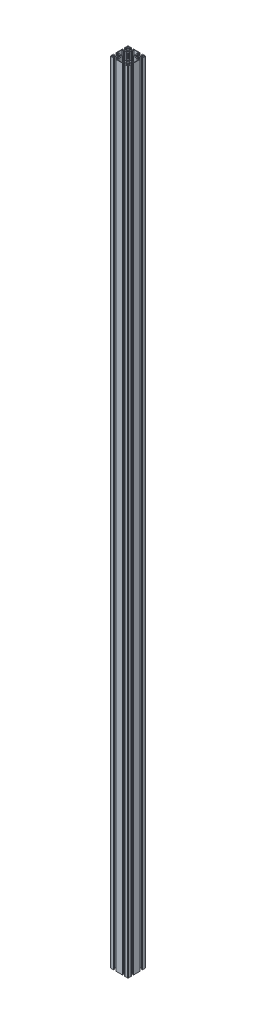
SolidWorks part; units mm, degrees
material "6061 Alloy"
ref_plane "Front Plane" through (0, 0, 0) normal (0, 0, 1) x (1, 0, 0)
ref_plane "Top Plane" through (0, 0, 0) normal (0, 1, 0) x (1, 0, 0)
ref_plane "Right Plane" through (0, 0, 0) normal (1, 0, 0) x (0, 0, -1)
sketch "Sketch1" plane through (0, 0, 0) normal (0, 1, 0) x (1, 0, 0)
  line L0 (505.2058, 27.1189) -> (507.2058, 27.1189)
  line L1 (507.2058, 25.1189) -> (496.7058, 25.1189)
  line L2 (495.7058, 26.1189) -> (495.7058, 36.6189)
  line L3 (497.7058, 36.6189) -> (497.7058, 34.6189)
  line L4 (498.7058, 33.6189) -> (503.8258, 33.6189)
  line L5 (504.2058, 33.2389) -> (504.2058, 28.1189)
  line L6 (522.0488, 41.8952) -> (520.4218, 42.9309)
  line L7 (518.8935, 41.4027) -> (519.9294, 39.776)
  line L8 (517.7043, 38.8542) -> (517.2863, 40.7371)
  line L9 (515.125, 40.7371) -> (514.7072, 38.8544)
  line L10 (512.482, 39.776) -> (513.5178, 41.4029)
  line L11 (511.9896, 42.9313) -> (510.3629, 41.8954)
  line L12 (509.4411, 44.1204) -> (511.324, 44.5385)
  line L13 (511.324, 46.6998) -> (509.4413, 47.1175)
  line L14 (510.3628, 49.3427) -> (511.9898, 48.3069)
  line L15 (513.5181, 49.8351) -> (512.4822, 51.4618)
  line L16 (514.7073, 52.3836) -> (515.1254, 50.5008)
  line L17 (517.2867, 50.5007) -> (517.7044, 52.3835)
  line L18 (519.9296, 51.4619) -> (518.8938, 49.8349)
  line L19 (520.422, 48.3066) -> (522.0487, 49.3425)
  line L20 (522.9705, 47.1174) -> (521.0877, 46.6994)
  line L21 (521.0876, 44.5381) -> (522.9703, 44.1203)
  line L22 (579.7058, 34.6189) -> (579.7058, 36.6189)
  line L23 (581.7058, 36.6189) -> (581.7058, 26.1189)
  line L24 (580.7058, 25.1189) -> (570.2058, 25.1189)
  line L25 (570.2058, 27.1189) -> (572.2058, 27.1189)
  line L26 (573.2058, 28.1189) -> (573.2058, 33.2389)
  line L27 (573.5858, 33.6189) -> (578.7058, 33.6189)
  line L28 (565.422, 48.3066) -> (567.0487, 49.3425)
  line L29 (567.9705, 47.1174) -> (566.0877, 46.6994)
  line L30 (566.0876, 44.5381) -> (567.9703, 44.1203)
  line L31 (567.0488, 41.8952) -> (565.4218, 42.9309)
  line L32 (563.8935, 41.4027) -> (564.9294, 39.776)
  line L33 (562.7043, 38.8542) -> (562.2863, 40.7371)
  line L34 (560.125, 40.7371) -> (559.7072, 38.8544)
  line L35 (557.482, 39.776) -> (558.5178, 41.4029)
  line L36 (556.9896, 42.9313) -> (555.3629, 41.8954)
  line L37 (554.4411, 44.1204) -> (556.324, 44.5385)
  line L38 (556.324, 46.6998) -> (554.4413, 47.1175)
  line L39 (555.3628, 49.3427) -> (556.9898, 48.3069)
  line L40 (558.5181, 49.8351) -> (557.4822, 51.4618)
  line L41 (559.7073, 52.3836) -> (560.1254, 50.5008)
  line L42 (562.2867, 50.5007) -> (562.7044, 52.3835)
  line L43 (564.9296, 51.4619) -> (563.8938, 49.8349)
  line L44 (573.2058, 102.9989) -> (573.2058, 108.1189)
  line L45 (572.2058, 109.1189) -> (570.2058, 109.1189)
  line L46 (570.2058, 111.1189) -> (580.7058, 111.1189)
  line L47 (581.7058, 110.1189) -> (581.7058, 99.6189)
  line L48 (579.7058, 99.6189) -> (579.7058, 101.6189)
  line L49 (578.7058, 102.6189) -> (573.5858, 102.6189)
  line L50 (565.422, 93.3066) -> (567.0487, 94.3425)
  line L51 (567.9705, 92.1174) -> (566.0877, 91.6994)
  line L52 (566.0876, 89.5381) -> (567.9703, 89.1203)
  line L53 (567.0488, 86.8952) -> (565.4218, 87.9309)
  line L54 (563.8935, 86.4027) -> (564.9294, 84.776)
  line L55 (562.7043, 83.8542) -> (562.2863, 85.7371)
  line L56 (560.125, 85.7371) -> (559.7072, 83.8544)
  line L57 (557.482, 84.776) -> (558.5178, 86.4029)
  line L58 (556.9896, 87.9313) -> (555.3629, 86.8954)
  line L59 (554.4411, 89.1204) -> (556.324, 89.5385)
  line L60 (556.324, 91.6998) -> (554.4413, 92.1175)
  line L61 (555.3628, 94.3427) -> (556.9898, 93.3069)
  line L62 (558.5181, 94.8351) -> (557.4822, 96.4618)
  line L63 (559.7073, 97.3836) -> (560.1254, 95.5008)
  line L64 (562.2867, 95.5007) -> (562.7044, 97.3835)
  line L65 (564.9296, 96.4619) -> (563.8938, 94.8349)
  line L66 (497.7058, 101.6189) -> (497.7058, 99.6189)
  line L67 (495.7058, 99.6189) -> (495.7058, 110.1189)
  line L68 (496.7058, 111.1189) -> (507.2058, 111.1189)
  line L69 (507.2058, 109.1189) -> (505.2058, 109.1189)
  line L70 (504.2058, 108.1189) -> (504.2058, 102.9989)
  line L71 (503.8258, 102.6189) -> (498.7058, 102.6189)
  line L72 (522.0488, 86.8952) -> (520.4218, 87.9309)
  line L73 (518.8935, 86.4027) -> (519.9294, 84.776)
  line L74 (517.7043, 83.8542) -> (517.2863, 85.7371)
  line L75 (515.125, 85.7371) -> (514.7072, 83.8544)
  line L76 (512.482, 84.776) -> (513.5178, 86.4029)
  line L77 (511.9896, 87.9313) -> (510.3629, 86.8954)
  line L78 (509.4411, 89.1204) -> (511.324, 89.5385)
  line L79 (511.324, 91.6998) -> (509.4413, 92.1175)
  line L80 (510.3628, 94.3427) -> (511.9898, 93.3069)
  line L81 (513.5181, 94.8351) -> (512.4822, 96.4618)
  line L82 (514.7073, 97.3836) -> (515.1254, 95.5008)
  line L83 (517.2867, 95.5007) -> (517.7044, 97.3835)
  line L84 (519.9296, 96.4619) -> (518.8938, 94.8349)
  line L85 (520.422, 93.3066) -> (522.0487, 94.3425)
  line L86 (522.9705, 92.1174) -> (521.0877, 91.6994)
  line L87 (521.0876, 89.5381) -> (522.9703, 89.1203)
  line L88 (577.7058, 57.9589) -> (572.0832, 57.9589)
  line L89 (570.669, 57.3731) -> (568.5261, 55.2302)
  line L90 (568.2574, 55.1189) -> (562.1058, 55.1189)
  line L91 (562.1058, 55.1189) -> (561.2058, 54.6038)
  line L92 (561.2058, 54.6038) -> (560.3058, 55.1189)
  line L93 (560.3058, 55.1189) -> (553.7058, 55.1189)
  line L94 (551.7058, 53.1189) -> (551.7058, 46.5189)
  line L95 (551.7058, 46.5189) -> (552.2254, 45.6189)
  line L96 (552.2254, 45.6189) -> (551.7058, 44.7189)
  line L97 (551.7058, 44.7189) -> (551.7058, 38.5674)
  line L98 (551.5945, 38.2987) -> (550.0845, 36.7886)
  line L99 (549.2058, 34.6673) -> (549.2058, 28.1189)
  line L100 (550.2058, 27.1189) -> (552.2058, 27.1189)
  line L101 (552.2058, 25.1189) -> (525.2058, 25.1189)
  line L102 (525.2058, 27.1189) -> (527.2058, 27.1189)
  line L103 (528.2058, 28.1189) -> (528.2058, 34.6673)
  line L104 (527.3271, 36.7886) -> (525.8171, 38.2987)
  line L105 (525.7058, 38.5674) -> (525.7058, 44.7189)
  line L106 (525.7058, 44.7189) -> (525.1862, 45.6189)
  line L107 (525.1862, 45.6189) -> (525.7058, 46.5189)
  line L108 (525.7058, 46.5189) -> (525.7058, 53.1189)
  line L109 (523.7058, 55.1189) -> (517.1058, 55.1189)
  line L110 (517.1058, 55.1189) -> (516.2058, 54.6038)
  line L111 (516.2058, 54.6038) -> (515.3058, 55.1189)
  line L112 (515.3058, 55.1189) -> (509.1542, 55.1189)
  line L113 (508.8855, 55.2302) -> (506.7426, 57.3731)
  line L114 (505.3284, 57.9589) -> (499.7058, 57.9589)
  line L115 (497.7058, 55.9589) -> (497.7058, 54.6189)
  line L116 (495.7058, 54.6189) -> (495.7058, 81.6189)
  line L117 (497.7058, 81.6189) -> (497.7058, 80.2789)
  line L118 (499.7058, 78.2789) -> (505.3284, 78.2789)
  line L119 (506.7426, 78.8647) -> (508.8855, 81.0076)
  line L120 (509.1542, 81.1189) -> (515.3058, 81.1189)
  line L121 (515.3058, 81.1189) -> (516.2058, 81.6341)
  line L122 (516.2058, 81.6341) -> (517.1058, 81.1189)
  line L123 (517.1058, 81.1189) -> (523.7058, 81.1189)
  line L124 (525.7058, 83.1189) -> (525.7058, 89.7189)
  line L125 (525.7058, 89.7189) -> (525.1862, 90.6189)
  line L126 (525.1862, 90.6189) -> (525.7058, 91.5189)
  line L127 (525.7058, 91.5189) -> (525.7058, 97.6705)
  line L128 (525.8171, 97.9392) -> (527.3271, 99.4492)
  line L129 (528.2058, 101.5705) -> (528.2058, 108.1189)
  line L130 (527.2058, 109.1189) -> (525.2058, 109.1189)
  line L131 (525.2058, 111.1189) -> (552.2058, 111.1189)
  line L132 (552.2058, 109.1189) -> (550.2058, 109.1189)
  line L133 (549.2058, 108.1189) -> (549.2058, 101.5705)
  line L134 (550.0845, 99.4492) -> (551.5945, 97.9392)
  line L135 (551.7058, 97.6705) -> (551.7058, 91.5189)
  line L136 (551.7058, 91.5189) -> (552.2254, 90.6189)
  line L137 (552.2254, 90.6189) -> (551.7058, 89.7189)
  line L138 (551.7058, 89.7189) -> (551.7058, 83.1189)
  line L139 (553.7058, 81.1189) -> (560.3058, 81.1189)
  line L140 (560.3058, 81.1189) -> (561.2058, 81.6341)
  line L141 (561.2058, 81.6341) -> (562.1058, 81.1189)
  line L142 (562.1058, 81.1189) -> (568.2574, 81.1189)
  line L143 (568.5261, 81.0076) -> (570.6639, 78.8698)
  line L144 (572.0781, 78.284) -> (577.7058, 78.284)
  line L145 (579.7058, 80.284) -> (579.7058, 81.6189)
  line L146 (581.7058, 81.6189) -> (581.7058, 54.6189)
  line L147 (579.7058, 54.6189) -> (579.7058, 55.9589)
  line L148 (583.7058, 52.2039) -> (583.7058, 84.0339)
  line L149 (582.1858, 85.5539) -> (579.2258, 85.5539)
  line L150 (577.7058, 84.0339) -> (577.7058, 81.5689)
  line L151 (576.7058, 80.5689) -> (573.7042, 80.5689)
  line L152 (573.4355, 80.6802) -> (570.8171, 83.2987)
  line L153 (570.7058, 83.5674) -> (570.7058, 89.7189)
  line L154 (570.7058, 89.7189) -> (570.1862, 90.6189)
  line L155 (570.1862, 90.6189) -> (570.7058, 91.5189)
  line L156 (570.7058, 91.5189) -> (570.7058, 97.6705)
  line L157 (570.8171, 97.9392) -> (573.4355, 100.5576)
  line L158 (573.7042, 100.6689) -> (576.7058, 100.6689)
  line L159 (577.7058, 99.6689) -> (577.7058, 97.2039)
  line L160 (579.2258, 95.6839) -> (582.1858, 95.6839)
  line L161 (583.7058, 97.2039) -> (583.7058, 110.1189)
  line L162 (580.7058, 113.1189) -> (567.7908, 113.1189)
  line L163 (566.2708, 111.5989) -> (566.2708, 108.6389)
  line L164 (567.7908, 107.1189) -> (570.2558, 107.1189)
  line L165 (571.2558, 106.1189) -> (571.2558, 103.1174)
  line L166 (571.1445, 102.8487) -> (568.5261, 100.2302)
  line L167 (568.2574, 100.1189) -> (562.1058, 100.1189)
  line L168 (562.1058, 100.1189) -> (561.2058, 99.6038)
  line L169 (561.2058, 99.6038) -> (560.3058, 100.1189)
  line L170 (560.3058, 100.1189) -> (554.1542, 100.1189)
  line L171 (553.8855, 100.2302) -> (551.2671, 102.8487)
  line L172 (551.1558, 103.1174) -> (551.1558, 106.1189)
  line L173 (552.1558, 107.1189) -> (554.6208, 107.1189)
  line L174 (556.1408, 108.6389) -> (556.1408, 111.5989)
  line L175 (554.6208, 113.1189) -> (522.7908, 113.1189)
  line L176 (521.2708, 111.5989) -> (521.2708, 108.6389)
  line L177 (522.7908, 107.1189) -> (525.2558, 107.1189)
  line L178 (526.2558, 106.1189) -> (526.2558, 103.1174)
  line L179 (526.1445, 102.8487) -> (523.5261, 100.2302)
  line L180 (523.2574, 100.1189) -> (517.1058, 100.1189)
  line L181 (517.1058, 100.1189) -> (516.2058, 99.6038)
  line L182 (516.2058, 99.6038) -> (515.3058, 100.1189)
  line L183 (515.3058, 100.1189) -> (509.1542, 100.1189)
  line L184 (508.8855, 100.2302) -> (506.2671, 102.8487)
  line L185 (506.1558, 103.1174) -> (506.1558, 106.1189)
  line L186 (507.1558, 107.1189) -> (509.6208, 107.1189)
  line L187 (511.1408, 108.6389) -> (511.1408, 111.5989)
  line L188 (509.6208, 113.1189) -> (496.7058, 113.1189)
  line L189 (493.7058, 110.1189) -> (493.7058, 97.2039)
  line L190 (495.2258, 95.6839) -> (498.1858, 95.6839)
  line L191 (499.7058, 97.2039) -> (499.7058, 99.6689)
  line L192 (500.7058, 100.6689) -> (503.7074, 100.6689)
  line L193 (503.9761, 100.5576) -> (506.5945, 97.9392)
  line L194 (506.7058, 97.6705) -> (506.7058, 91.5189)
  line L195 (506.7058, 91.5189) -> (507.2254, 90.6189)
  line L196 (507.2254, 90.6189) -> (506.7058, 89.7189)
  line L197 (506.7058, 89.7189) -> (506.7058, 83.5674)
  line L198 (506.5945, 83.2987) -> (503.9761, 80.6802)
  line L199 (503.7074, 80.5689) -> (500.7058, 80.5689)
  line L200 (499.7058, 81.5689) -> (499.7058, 84.0339)
  line L201 (498.1858, 85.5539) -> (495.2258, 85.5539)
  line L202 (493.7058, 84.0339) -> (493.7058, 52.2039)
  line L203 (495.2258, 50.6839) -> (498.1858, 50.6839)
  line L204 (499.7058, 52.2039) -> (499.7058, 54.6689)
  line L205 (500.7058, 55.6689) -> (503.7074, 55.6689)
  line L206 (503.9761, 55.5576) -> (506.5945, 52.9392)
  line L207 (506.7058, 52.6705) -> (506.7058, 46.5189)
  line L208 (506.7058, 46.5189) -> (507.2254, 45.6189)
  line L209 (507.2254, 45.6189) -> (506.7058, 44.7189)
  line L210 (506.7058, 44.7189) -> (506.7058, 38.5674)
  line L211 (506.5945, 38.2987) -> (503.9761, 35.6802)
  line L212 (503.7074, 35.5689) -> (500.7058, 35.5689)
  line L213 (499.7058, 36.5689) -> (499.7058, 39.0339)
  line L214 (498.1858, 40.5539) -> (495.2258, 40.5539)
  line L215 (493.7058, 39.0339) -> (493.7058, 26.1189)
  line L216 (496.7058, 23.1189) -> (509.6208, 23.1189)
  line L217 (511.1408, 24.6389) -> (511.1408, 27.5989)
  line L218 (509.6208, 29.1189) -> (507.1558, 29.1189)
  line L219 (506.1558, 30.1189) -> (506.1558, 33.1205)
  line L220 (506.2671, 33.3892) -> (508.8855, 36.0076)
  line L221 (509.1542, 36.1189) -> (515.3058, 36.1189)
  line L222 (515.3058, 36.1189) -> (516.2058, 36.6341)
  line L223 (516.2058, 36.6341) -> (517.1058, 36.1189)
  line L224 (517.1058, 36.1189) -> (523.2574, 36.1189)
  line L225 (523.5261, 36.0076) -> (526.1445, 33.3892)
  line L226 (526.2558, 33.1205) -> (526.2558, 30.1189)
  line L227 (525.2558, 29.1189) -> (522.7908, 29.1189)
  line L228 (521.2708, 27.5989) -> (521.2708, 24.6389)
  line L229 (522.7908, 23.1189) -> (554.6208, 23.1189)
  line L230 (556.1408, 24.6389) -> (556.1408, 27.5989)
  line L231 (554.6208, 29.1189) -> (552.1558, 29.1189)
  line L232 (551.1558, 30.1189) -> (551.1558, 33.1205)
  line L233 (551.2671, 33.3892) -> (553.8855, 36.0076)
  line L234 (554.1542, 36.1189) -> (560.3058, 36.1189)
  line L235 (560.3058, 36.1189) -> (561.2058, 36.6341)
  line L236 (561.2058, 36.6341) -> (562.1058, 36.1189)
  line L237 (562.1058, 36.1189) -> (568.2574, 36.1189)
  line L238 (568.5261, 36.0076) -> (571.1445, 33.3892)
  line L239 (571.2558, 33.1205) -> (571.2558, 30.1189)
  line L240 (570.2558, 29.1189) -> (567.7908, 29.1189)
  line L241 (566.2708, 27.5989) -> (566.2708, 24.6389)
  line L242 (567.7908, 23.1189) -> (580.7058, 23.1189)
  line L243 (583.7058, 26.1189) -> (583.7058, 39.0339)
  line L244 (582.1858, 40.5539) -> (579.2258, 40.5539)
  line L245 (577.7058, 39.0339) -> (577.7058, 36.5689)
  line L246 (576.7058, 35.5689) -> (573.7042, 35.5689)
  line L247 (573.4355, 35.6802) -> (570.8171, 38.2987)
  line L248 (570.7058, 38.5674) -> (570.7058, 44.7189)
  line L249 (570.7058, 44.7189) -> (570.1862, 45.6189)
  line L250 (570.1862, 45.6189) -> (570.7058, 46.5189)
  line L251 (570.7058, 46.5189) -> (570.7058, 52.6705)
  line L252 (570.8171, 52.9392) -> (573.4355, 55.5576)
  line L253 (573.7042, 55.6689) -> (576.7058, 55.6689)
  line L254 (577.7058, 54.6689) -> (577.7058, 52.2039)
  line L255 (579.2258, 50.6839) -> (582.1858, 50.6839)
  arc A0 (504.2058, 28.1189) -> (505.2058, 27.1189) centre (505.2058, 28.1189) ccw
  arc A1 (507.2058, 25.1189) -> (507.2058, 27.1189) centre (507.2058, 26.1189) ccw
  arc A2 (495.7058, 26.1189) -> (496.7058, 25.1189) centre (496.7058, 26.1189) ccw
  arc A3 (497.7058, 36.6189) -> (495.7058, 36.6189) centre (496.7058, 36.6189) ccw
  arc A4 (497.7058, 34.6189) -> (498.7058, 33.6189) centre (498.7058, 34.6189) ccw
  arc A5 (504.2058, 33.2389) -> (503.8258, 33.6189) centre (503.8258, 33.2389) ccw
  arc A6 (523.4972, 42.3273) -> (523.6891, 42.7905) centre (516.2058, 45.6189) ccw
  arc A7 (522.0488, 41.8952) -> (523.4972, 42.3273) centre (522.5858, 42.7387) ccw
  arc A8 (518.8935, 41.4027) -> (520.4218, 42.9309) centre (516.2058, 45.6189) ccw
  arc A9 (519.4973, 38.3274) -> (519.9294, 39.776) centre (519.0859, 39.2389) ccw
  arc A10 (519.0341, 38.1355) -> (519.4973, 38.3274) centre (516.2058, 45.6189) ccw
  arc A11 (517.7043, 38.8542) -> (519.0341, 38.1355) centre (518.6805, 39.071) ccw
  arc A12 (515.125, 40.7371) -> (517.2863, 40.7371) centre (516.2058, 45.6189) ccw
  arc A13 (513.3774, 38.1356) -> (514.7072, 38.8544) centre (513.731, 39.071) ccw
  arc A14 (512.9142, 38.3275) -> (513.3774, 38.1356) centre (516.2058, 45.6189) ccw
  arc A15 (512.482, 39.776) -> (512.9142, 38.3275) centre (513.3256, 39.2389) ccw
  arc A16 (511.9896, 42.9313) -> (513.5178, 41.4029) centre (516.2058, 45.6189) ccw
  arc A17 (508.9143, 42.3274) -> (510.3629, 41.8954) centre (509.8258, 42.7388) ccw
  arc A18 (508.7224, 42.7907) -> (508.9143, 42.3274) centre (516.2058, 45.6189) ccw
  arc A19 (509.4411, 44.1204) -> (508.7224, 42.7907) centre (509.6579, 43.1442) ccw
  arc A20 (511.324, 46.6998) -> (511.324, 44.5385) centre (516.2058, 45.6189) ccw
  arc A21 (508.7225, 48.4473) -> (509.4413, 47.1175) centre (509.6579, 48.0938) ccw
  arc A22 (508.9144, 48.9106) -> (508.7225, 48.4473) centre (516.2058, 45.6189) ccw
  arc A23 (510.3628, 49.3427) -> (508.9144, 48.9106) centre (509.8258, 48.4991) ccw
  arc A24 (513.5181, 49.8351) -> (511.9898, 48.3069) centre (516.2058, 45.6189) ccw
  arc A25 (512.9143, 52.9104) -> (512.4822, 51.4618) centre (513.3257, 51.999) ccw
  arc A26 (513.3776, 53.1023) -> (512.9143, 52.9104) centre (516.2058, 45.6189) ccw
  arc A27 (514.7073, 52.3836) -> (513.3776, 53.1023) centre (513.7311, 52.1669) ccw
  arc A28 (517.2867, 50.5007) -> (515.1254, 50.5008) centre (516.2058, 45.6189) ccw
  arc A29 (519.0342, 53.1022) -> (517.7044, 52.3835) centre (518.6807, 52.1668) ccw
  arc A30 (519.4975, 52.9104) -> (519.0342, 53.1022) centre (516.2058, 45.6189) ccw
  arc A31 (519.9296, 51.4619) -> (519.4975, 52.9104) centre (519.086, 51.9989) ccw
  arc A32 (520.422, 48.3066) -> (518.8938, 49.8349) centre (516.2058, 45.6189) ccw
  arc A33 (523.4973, 48.9104) -> (522.0487, 49.3425) centre (522.5859, 48.499) ccw
  arc A34 (523.6892, 48.4472) -> (523.4973, 48.9104) centre (516.2058, 45.6189) ccw
  arc A35 (522.9705, 47.1174) -> (523.6892, 48.4472) centre (522.7538, 48.0937) ccw
  arc A36 (521.0876, 44.5381) -> (521.0877, 46.6994) centre (516.2058, 45.6189) ccw
  arc A37 (523.6891, 42.7905) -> (522.9703, 44.1203) centre (522.7537, 43.1441) ccw
  arc A38 (578.7058, 33.6189) -> (579.7058, 34.6189) centre (578.7058, 34.6189) ccw
  arc A39 (581.7058, 36.6189) -> (579.7058, 36.6189) centre (580.7058, 36.6189) ccw
  arc A40 (580.7058, 25.1189) -> (581.7058, 26.1189) centre (580.7058, 26.1189) ccw
  arc A41 (570.2058, 27.1189) -> (570.2058, 25.1189) centre (570.2058, 26.1189) ccw
  arc A42 (572.2058, 27.1189) -> (573.2058, 28.1189) centre (572.2058, 28.1189) ccw
  arc A43 (573.5858, 33.6189) -> (573.2058, 33.2389) centre (573.5858, 33.2389) ccw
  arc A44 (565.422, 48.3066) -> (563.8938, 49.8349) centre (561.2058, 45.6189) ccw
  arc A45 (568.4973, 48.9104) -> (567.0487, 49.3425) centre (567.5859, 48.499) ccw
  arc A46 (568.6892, 48.4472) -> (568.4973, 48.9104) centre (561.2058, 45.6189) ccw
  arc A47 (567.9705, 47.1174) -> (568.6892, 48.4472) centre (567.7538, 48.0937) ccw
  arc A48 (566.0876, 44.5381) -> (566.0877, 46.6994) centre (561.2058, 45.6189) ccw
  arc A49 (568.6891, 42.7905) -> (567.9703, 44.1203) centre (567.7537, 43.1441) ccw
  arc A50 (568.4972, 42.3273) -> (568.6891, 42.7905) centre (561.2058, 45.6189) ccw
  arc A51 (567.0488, 41.8952) -> (568.4972, 42.3273) centre (567.5858, 42.7387) ccw
  arc A52 (563.8935, 41.4027) -> (565.4218, 42.9309) centre (561.2058, 45.6189) ccw
  arc A53 (564.4973, 38.3274) -> (564.9294, 39.776) centre (564.0859, 39.2389) ccw
  arc A54 (564.0341, 38.1355) -> (564.4973, 38.3274) centre (561.2058, 45.6189) ccw
  arc A55 (562.7043, 38.8542) -> (564.0341, 38.1355) centre (563.6805, 39.071) ccw
  arc A56 (560.125, 40.7371) -> (562.2863, 40.7371) centre (561.2058, 45.6189) ccw
  arc A57 (558.3774, 38.1356) -> (559.7072, 38.8544) centre (558.731, 39.071) ccw
  arc A58 (557.9142, 38.3275) -> (558.3774, 38.1356) centre (561.2058, 45.6189) ccw
  arc A59 (557.482, 39.776) -> (557.9142, 38.3275) centre (558.3256, 39.2389) ccw
  arc A60 (556.9896, 42.9313) -> (558.5178, 41.4029) centre (561.2058, 45.6189) ccw
  arc A61 (553.9143, 42.3274) -> (555.3629, 41.8954) centre (554.8258, 42.7388) ccw
  arc A62 (553.7224, 42.7907) -> (553.9143, 42.3274) centre (561.2058, 45.6189) ccw
  arc A63 (554.4411, 44.1204) -> (553.7224, 42.7907) centre (554.6579, 43.1442) ccw
  arc A64 (556.324, 46.6998) -> (556.324, 44.5385) centre (561.2058, 45.6189) ccw
  arc A65 (553.7225, 48.4473) -> (554.4413, 47.1175) centre (554.6579, 48.0938) ccw
  arc A66 (553.9144, 48.9106) -> (553.7225, 48.4473) centre (561.2058, 45.6189) ccw
  arc A67 (555.3628, 49.3427) -> (553.9144, 48.9106) centre (554.8258, 48.4991) ccw
  arc A68 (558.5181, 49.8351) -> (556.9898, 48.3069) centre (561.2058, 45.6189) ccw
  arc A69 (557.9143, 52.9104) -> (557.4822, 51.4618) centre (558.3257, 51.999) ccw
  arc A70 (558.3776, 53.1023) -> (557.9143, 52.9104) centre (561.2058, 45.6189) ccw
  arc A71 (559.7073, 52.3836) -> (558.3776, 53.1023) centre (558.7311, 52.1669) ccw
  arc A72 (562.2867, 50.5007) -> (560.1254, 50.5008) centre (561.2058, 45.6189) ccw
  arc A73 (564.0342, 53.1022) -> (562.7044, 52.3835) centre (563.6807, 52.1668) ccw
  arc A74 (564.4975, 52.9104) -> (564.0342, 53.1022) centre (561.2058, 45.6189) ccw
  arc A75 (564.9296, 51.4619) -> (564.4975, 52.9104) centre (564.086, 51.9989) ccw
  arc A76 (573.2058, 102.9989) -> (573.5858, 102.6189) centre (573.5858, 102.9989) ccw
  arc A77 (573.2058, 108.1189) -> (572.2058, 109.1189) centre (572.2058, 108.1189) ccw
  arc A78 (570.2058, 111.1189) -> (570.2058, 109.1189) centre (570.2058, 110.1189) ccw
  arc A79 (581.7058, 110.1189) -> (580.7058, 111.1189) centre (580.7058, 110.1189) ccw
  arc A80 (579.7058, 99.6189) -> (581.7058, 99.6189) centre (580.7058, 99.6189) ccw
  arc A81 (579.7058, 101.6189) -> (578.7058, 102.6189) centre (578.7058, 101.6189) ccw
  arc A82 (565.422, 93.3066) -> (563.8938, 94.8349) centre (561.2058, 90.6189) ccw
  arc A83 (568.4973, 93.9104) -> (567.0487, 94.3425) centre (567.5859, 93.499) ccw
  arc A84 (568.6892, 93.4472) -> (568.4973, 93.9104) centre (561.2058, 90.6189) ccw
  arc A85 (567.9705, 92.1174) -> (568.6892, 93.4472) centre (567.7538, 93.0937) ccw
  arc A86 (566.0876, 89.5381) -> (566.0877, 91.6994) centre (561.2058, 90.6189) ccw
  arc A87 (568.6891, 87.7905) -> (567.9703, 89.1203) centre (567.7537, 88.1441) ccw
  arc A88 (568.4972, 87.3273) -> (568.6891, 87.7905) centre (561.2058, 90.6189) ccw
  arc A89 (567.0488, 86.8952) -> (568.4972, 87.3273) centre (567.5858, 87.7387) ccw
  arc A90 (563.8935, 86.4027) -> (565.4218, 87.9309) centre (561.2058, 90.6189) ccw
  arc A91 (564.4973, 83.3274) -> (564.9294, 84.776) centre (564.0859, 84.2389) ccw
  arc A92 (564.0341, 83.1355) -> (564.4973, 83.3274) centre (561.2058, 90.6189) ccw
  arc A93 (562.7043, 83.8542) -> (564.0341, 83.1355) centre (563.6805, 84.071) ccw
  arc A94 (560.125, 85.7371) -> (562.2863, 85.7371) centre (561.2058, 90.6189) ccw
  arc A95 (558.3774, 83.1356) -> (559.7072, 83.8544) centre (558.731, 84.071) ccw
  arc A96 (557.9142, 83.3275) -> (558.3774, 83.1356) centre (561.2058, 90.6189) ccw
  arc A97 (557.482, 84.776) -> (557.9142, 83.3275) centre (558.3256, 84.2389) ccw
  arc A98 (556.9896, 87.9313) -> (558.5178, 86.4029) centre (561.2058, 90.6189) ccw
  arc A99 (553.9143, 87.3274) -> (555.3629, 86.8954) centre (554.8258, 87.7388) ccw
  arc A100 (553.7224, 87.7907) -> (553.9143, 87.3274) centre (561.2058, 90.6189) ccw
  arc A101 (554.4411, 89.1204) -> (553.7224, 87.7907) centre (554.6579, 88.1442) ccw
  arc A102 (556.324, 91.6998) -> (556.324, 89.5385) centre (561.2058, 90.6189) ccw
  arc A103 (553.7225, 93.4473) -> (554.4413, 92.1175) centre (554.6579, 93.0938) ccw
  arc A104 (553.9144, 93.9106) -> (553.7225, 93.4473) centre (561.2058, 90.6189) ccw
  arc A105 (555.3628, 94.3427) -> (553.9144, 93.9106) centre (554.8258, 93.4991) ccw
  arc A106 (558.5181, 94.8351) -> (556.9898, 93.3069) centre (561.2058, 90.6189) ccw
  arc A107 (557.9143, 97.9104) -> (557.4822, 96.4618) centre (558.3257, 96.999) ccw
  arc A108 (558.3776, 98.1023) -> (557.9143, 97.9104) centre (561.2058, 90.6189) ccw
  arc A109 (559.7073, 97.3836) -> (558.3776, 98.1023) centre (558.7311, 97.1669) ccw
  arc A110 (562.2867, 95.5007) -> (560.1254, 95.5008) centre (561.2058, 90.6189) ccw
  arc A111 (564.0342, 98.1022) -> (562.7044, 97.3835) centre (563.6807, 97.1668) ccw
  arc A112 (564.4975, 97.9104) -> (564.0342, 98.1022) centre (561.2058, 90.6189) ccw
  arc A113 (564.9296, 96.4619) -> (564.4975, 97.9104) centre (564.086, 96.9989) ccw
  arc A114 (498.7058, 102.6189) -> (497.7058, 101.6189) centre (498.7058, 101.6189) ccw
  arc A115 (495.7058, 99.6189) -> (497.7058, 99.6189) centre (496.7058, 99.6189) ccw
  arc A116 (496.7058, 111.1189) -> (495.7058, 110.1189) centre (496.7058, 110.1189) ccw
  arc A117 (507.2058, 109.1189) -> (507.2058, 111.1189) centre (507.2058, 110.1189) ccw
  arc A118 (505.2058, 109.1189) -> (504.2058, 108.1189) centre (505.2058, 108.1189) ccw
  arc A119 (503.8258, 102.6189) -> (504.2058, 102.9989) centre (503.8258, 102.9989) ccw
  arc A120 (523.4972, 87.3273) -> (523.6891, 87.7905) centre (516.2058, 90.6189) ccw
  arc A121 (522.0488, 86.8952) -> (523.4972, 87.3273) centre (522.5858, 87.7387) ccw
  arc A122 (518.8935, 86.4027) -> (520.4218, 87.9309) centre (516.2058, 90.6189) ccw
  arc A123 (519.4973, 83.3274) -> (519.9294, 84.776) centre (519.0859, 84.2389) ccw
  arc A124 (519.0341, 83.1355) -> (519.4973, 83.3274) centre (516.2058, 90.6189) ccw
  arc A125 (517.7043, 83.8542) -> (519.0341, 83.1355) centre (518.6805, 84.071) ccw
  arc A126 (515.125, 85.7371) -> (517.2863, 85.7371) centre (516.2058, 90.6189) ccw
  arc A127 (513.3774, 83.1356) -> (514.7072, 83.8544) centre (513.731, 84.071) ccw
  arc A128 (512.9142, 83.3275) -> (513.3774, 83.1356) centre (516.2058, 90.6189) ccw
  arc A129 (512.482, 84.776) -> (512.9142, 83.3275) centre (513.3256, 84.2389) ccw
  arc A130 (511.9896, 87.9313) -> (513.5178, 86.4029) centre (516.2058, 90.6189) ccw
  arc A131 (508.9143, 87.3274) -> (510.3629, 86.8954) centre (509.8258, 87.7388) ccw
  arc A132 (508.7224, 87.7907) -> (508.9143, 87.3274) centre (516.2058, 90.6189) ccw
  arc A133 (509.4411, 89.1204) -> (508.7224, 87.7907) centre (509.6579, 88.1442) ccw
  arc A134 (511.324, 91.6998) -> (511.324, 89.5385) centre (516.2058, 90.6189) ccw
  arc A135 (508.7225, 93.4473) -> (509.4413, 92.1175) centre (509.6579, 93.0938) ccw
  arc A136 (508.9144, 93.9106) -> (508.7225, 93.4473) centre (516.2058, 90.6189) ccw
  arc A137 (510.3628, 94.3427) -> (508.9144, 93.9106) centre (509.8258, 93.4991) ccw
  arc A138 (513.5181, 94.8351) -> (511.9898, 93.3069) centre (516.2058, 90.6189) ccw
  arc A139 (512.9143, 97.9104) -> (512.4822, 96.4618) centre (513.3257, 96.999) ccw
  arc A140 (513.3776, 98.1023) -> (512.9143, 97.9104) centre (516.2058, 90.6189) ccw
  arc A141 (514.7073, 97.3836) -> (513.3776, 98.1023) centre (513.7311, 97.1669) ccw
  arc A142 (517.2867, 95.5007) -> (515.1254, 95.5008) centre (516.2058, 90.6189) ccw
  arc A143 (519.0342, 98.1022) -> (517.7044, 97.3835) centre (518.6807, 97.1668) ccw
  arc A144 (519.4975, 97.9104) -> (519.0342, 98.1022) centre (516.2058, 90.6189) ccw
  arc A145 (519.9296, 96.4619) -> (519.4975, 97.9104) centre (519.086, 96.9989) ccw
  arc A146 (520.422, 93.3066) -> (518.8938, 94.8349) centre (516.2058, 90.6189) ccw
  arc A147 (523.4973, 93.9104) -> (522.0487, 94.3425) centre (522.5859, 93.499) ccw
  arc A148 (523.6892, 93.4472) -> (523.4973, 93.9104) centre (516.2058, 90.6189) ccw
  arc A149 (522.9705, 92.1174) -> (523.6892, 93.4472) centre (522.7538, 93.0937) ccw
  arc A150 (521.0876, 89.5381) -> (521.0877, 91.6994) centre (516.2058, 90.6189) ccw
  arc A151 (523.6891, 87.7905) -> (522.9703, 89.1203) centre (522.7537, 88.1441) ccw
  arc A152 (579.7058, 55.9589) -> (577.7058, 57.9589) centre (577.7058, 55.9589) ccw
  arc A153 (572.0832, 57.9589) -> (570.669, 57.3731) centre (572.0832, 55.9589) ccw
  arc A154 (568.2574, 55.1189) -> (568.5261, 55.2302) centre (568.2574, 55.4989) ccw
  arc A155 (553.7058, 55.1189) -> (551.7058, 53.1189) centre (553.7058, 53.1189) ccw
  arc A156 (551.5945, 38.2987) -> (551.7058, 38.5674) centre (551.3258, 38.5674) ccw
  arc A157 (550.0845, 36.7886) -> (549.2058, 34.6673) centre (552.2058, 34.6673) ccw
  arc A158 (549.2058, 28.1189) -> (550.2058, 27.1189) centre (550.2058, 28.1189) ccw
  arc A159 (552.2058, 25.1189) -> (552.2058, 27.1189) centre (552.2058, 26.1189) ccw
  arc A160 (525.2058, 27.1189) -> (525.2058, 25.1189) centre (525.2058, 26.1189) ccw
  arc A161 (527.2058, 27.1189) -> (528.2058, 28.1189) centre (527.2058, 28.1189) ccw
  arc A162 (528.2058, 34.6673) -> (527.3271, 36.7886) centre (525.2058, 34.6673) ccw
  arc A163 (525.7058, 38.5674) -> (525.8171, 38.2987) centre (526.0858, 38.5674) ccw
  arc A164 (525.7058, 53.1189) -> (523.7058, 55.1189) centre (523.7058, 53.1189) ccw
  arc A165 (508.8855, 55.2302) -> (509.1542, 55.1189) centre (509.1542, 55.4989) ccw
  arc A166 (506.7426, 57.3731) -> (505.3284, 57.9589) centre (505.3284, 55.9589) ccw
  arc A167 (499.7058, 57.9589) -> (497.7058, 55.9589) centre (499.7058, 55.9589) ccw
  arc A168 (495.7058, 54.6189) -> (497.7058, 54.6189) centre (496.7058, 54.6189) ccw
  arc A169 (497.7058, 81.6189) -> (495.7058, 81.6189) centre (496.7058, 81.6189) ccw
  arc A170 (497.7058, 80.2789) -> (499.7058, 78.2789) centre (499.7058, 80.2789) ccw
  arc A171 (505.3284, 78.2789) -> (506.7426, 78.8647) centre (505.3284, 80.2789) ccw
  arc A172 (509.1542, 81.1189) -> (508.8855, 81.0076) centre (509.1542, 80.7389) ccw
  arc A173 (523.7058, 81.1189) -> (525.7058, 83.1189) centre (523.7058, 83.1189) ccw
  arc A174 (525.8171, 97.9392) -> (525.7058, 97.6705) centre (526.0858, 97.6705) ccw
  arc A175 (527.3271, 99.4492) -> (528.2058, 101.5705) centre (525.2058, 101.5705) ccw
  arc A176 (528.2058, 108.1189) -> (527.2058, 109.1189) centre (527.2058, 108.1189) ccw
  arc A177 (525.2058, 111.1189) -> (525.2058, 109.1189) centre (525.2058, 110.1189) ccw
  arc A178 (552.2058, 109.1189) -> (552.2058, 111.1189) centre (552.2058, 110.1189) ccw
  arc A179 (550.2058, 109.1189) -> (549.2058, 108.1189) centre (550.2058, 108.1189) ccw
  arc A180 (549.2058, 101.5705) -> (550.0845, 99.4492) centre (552.2058, 101.5705) ccw
  arc A181 (551.7058, 97.6705) -> (551.5945, 97.9392) centre (551.3258, 97.6705) ccw
  arc A182 (551.7058, 83.1189) -> (553.7058, 81.1189) centre (553.7058, 83.1189) ccw
  arc A183 (568.5261, 81.0076) -> (568.2574, 81.1189) centre (568.2574, 80.7389) ccw
  arc A184 (570.6639, 78.8698) -> (572.0781, 78.284) centre (572.0781, 80.284) ccw
  arc A185 (577.7058, 78.284) -> (579.7058, 80.284) centre (577.7058, 80.284) ccw
  arc A186 (581.7058, 81.6189) -> (579.7058, 81.6189) centre (580.7058, 81.6189) ccw
  arc A187 (579.7058, 54.6189) -> (581.7058, 54.6189) centre (580.7058, 54.6189) ccw
  arc A188 (583.7058, 84.0339) -> (582.1858, 85.5539) centre (582.1858, 84.0339) ccw
  arc A189 (579.2258, 85.5539) -> (577.7058, 84.0339) centre (579.2258, 84.0339) ccw
  arc A190 (576.7058, 80.5689) -> (577.7058, 81.5689) centre (576.7058, 81.5689) ccw
  arc A191 (573.4355, 80.6802) -> (573.7042, 80.5689) centre (573.7042, 80.9489) ccw
  arc A192 (570.7058, 83.5674) -> (570.8171, 83.2987) centre (571.0858, 83.5674) ccw
  arc A193 (570.8171, 97.9392) -> (570.7058, 97.6705) centre (571.0858, 97.6705) ccw
  arc A194 (573.7042, 100.6689) -> (573.4355, 100.5576) centre (573.7042, 100.2889) ccw
  arc A195 (577.7058, 99.6689) -> (576.7058, 100.6689) centre (576.7058, 99.6689) ccw
  arc A196 (577.7058, 97.2039) -> (579.2258, 95.6839) centre (579.2258, 97.2039) ccw
  arc A197 (582.1858, 95.6839) -> (583.7058, 97.2039) centre (582.1858, 97.2039) ccw
  arc A198 (583.7058, 110.1189) -> (580.7058, 113.1189) centre (580.7058, 110.1189) ccw
  arc A199 (567.7908, 113.1189) -> (566.2708, 111.5989) centre (567.7908, 111.5989) ccw
  arc A200 (566.2708, 108.6389) -> (567.7908, 107.1189) centre (567.7908, 108.6389) ccw
  arc A201 (571.2558, 106.1189) -> (570.2558, 107.1189) centre (570.2558, 106.1189) ccw
  arc A202 (571.1445, 102.8487) -> (571.2558, 103.1174) centre (570.8758, 103.1174) ccw
  arc A203 (568.2574, 100.1189) -> (568.5261, 100.2302) centre (568.2574, 100.4989) ccw
  arc A204 (553.8855, 100.2302) -> (554.1542, 100.1189) centre (554.1542, 100.4989) ccw
  arc A205 (551.1558, 103.1174) -> (551.2671, 102.8487) centre (551.5358, 103.1174) ccw
  arc A206 (552.1558, 107.1189) -> (551.1558, 106.1189) centre (552.1558, 106.1189) ccw
  arc A207 (554.6208, 107.1189) -> (556.1408, 108.6389) centre (554.6208, 108.6389) ccw
  arc A208 (556.1408, 111.5989) -> (554.6208, 113.1189) centre (554.6208, 111.5989) ccw
  arc A209 (522.7908, 113.1189) -> (521.2708, 111.5989) centre (522.7908, 111.5989) ccw
  arc A210 (521.2708, 108.6389) -> (522.7908, 107.1189) centre (522.7908, 108.6389) ccw
  arc A211 (526.2558, 106.1189) -> (525.2558, 107.1189) centre (525.2558, 106.1189) ccw
  arc A212 (526.1445, 102.8487) -> (526.2558, 103.1174) centre (525.8758, 103.1174) ccw
  arc A213 (523.2574, 100.1189) -> (523.5261, 100.2302) centre (523.2574, 100.4989) ccw
  arc A214 (508.8855, 100.2302) -> (509.1542, 100.1189) centre (509.1542, 100.4989) ccw
  arc A215 (506.1558, 103.1174) -> (506.2671, 102.8487) centre (506.5358, 103.1174) ccw
  arc A216 (507.1558, 107.1189) -> (506.1558, 106.1189) centre (507.1558, 106.1189) ccw
  arc A217 (509.6208, 107.1189) -> (511.1408, 108.6389) centre (509.6208, 108.6389) ccw
  arc A218 (511.1408, 111.5989) -> (509.6208, 113.1189) centre (509.6208, 111.5989) ccw
  arc A219 (496.7058, 113.1189) -> (493.7058, 110.1189) centre (496.7058, 110.1189) ccw
  arc A220 (493.7058, 97.2039) -> (495.2258, 95.6839) centre (495.2258, 97.2039) ccw
  arc A221 (498.1858, 95.6839) -> (499.7058, 97.2039) centre (498.1858, 97.2039) ccw
  arc A222 (500.7058, 100.6689) -> (499.7058, 99.6689) centre (500.7058, 99.6689) ccw
  arc A223 (503.9761, 100.5576) -> (503.7074, 100.6689) centre (503.7074, 100.2889) ccw
  arc A224 (506.7058, 97.6705) -> (506.5945, 97.9392) centre (506.3258, 97.6705) ccw
  arc A225 (506.5945, 83.2987) -> (506.7058, 83.5674) centre (506.3258, 83.5674) ccw
  arc A226 (503.7074, 80.5689) -> (503.9761, 80.6802) centre (503.7074, 80.9489) ccw
  arc A227 (499.7058, 81.5689) -> (500.7058, 80.5689) centre (500.7058, 81.5689) ccw
  arc A228 (499.7058, 84.0339) -> (498.1858, 85.5539) centre (498.1858, 84.0339) ccw
  arc A229 (495.2258, 85.5539) -> (493.7058, 84.0339) centre (495.2258, 84.0339) ccw
  arc A230 (493.7058, 52.2039) -> (495.2258, 50.6839) centre (495.2258, 52.2039) ccw
  arc A231 (498.1858, 50.6839) -> (499.7058, 52.2039) centre (498.1858, 52.2039) ccw
  arc A232 (500.7058, 55.6689) -> (499.7058, 54.6689) centre (500.7058, 54.6689) ccw
  arc A233 (503.9761, 55.5576) -> (503.7074, 55.6689) centre (503.7074, 55.2889) ccw
  arc A234 (506.7058, 52.6705) -> (506.5945, 52.9392) centre (506.3258, 52.6705) ccw
  arc A235 (506.5945, 38.2987) -> (506.7058, 38.5674) centre (506.3258, 38.5674) ccw
  arc A236 (503.7074, 35.5689) -> (503.9761, 35.6802) centre (503.7074, 35.9489) ccw
  arc A237 (499.7058, 36.5689) -> (500.7058, 35.5689) centre (500.7058, 36.5689) ccw
  arc A238 (499.7058, 39.0339) -> (498.1858, 40.5539) centre (498.1858, 39.0339) ccw
  arc A239 (495.2258, 40.5539) -> (493.7058, 39.0339) centre (495.2258, 39.0339) ccw
  arc A240 (493.7058, 26.1189) -> (496.7058, 23.1189) centre (496.7058, 26.1189) ccw
  arc A241 (509.6208, 23.1189) -> (511.1408, 24.6389) centre (509.6208, 24.6389) ccw
  arc A242 (511.1408, 27.5989) -> (509.6208, 29.1189) centre (509.6208, 27.5989) ccw
  arc A243 (506.1558, 30.1189) -> (507.1558, 29.1189) centre (507.1558, 30.1189) ccw
  arc A244 (506.2671, 33.3892) -> (506.1558, 33.1205) centre (506.5358, 33.1205) ccw
  arc A245 (509.1542, 36.1189) -> (508.8855, 36.0076) centre (509.1542, 35.7389) ccw
  arc A246 (523.5261, 36.0076) -> (523.2574, 36.1189) centre (523.2574, 35.7389) ccw
  arc A247 (526.2558, 33.1205) -> (526.1445, 33.3892) centre (525.8758, 33.1205) ccw
  arc A248 (525.2558, 29.1189) -> (526.2558, 30.1189) centre (525.2558, 30.1189) ccw
  arc A249 (522.7908, 29.1189) -> (521.2708, 27.5989) centre (522.7908, 27.5989) ccw
  arc A250 (521.2708, 24.6389) -> (522.7908, 23.1189) centre (522.7908, 24.6389) ccw
  arc A251 (554.6208, 23.1189) -> (556.1408, 24.6389) centre (554.6208, 24.6389) ccw
  arc A252 (556.1408, 27.5989) -> (554.6208, 29.1189) centre (554.6208, 27.5989) ccw
  arc A253 (551.1558, 30.1189) -> (552.1558, 29.1189) centre (552.1558, 30.1189) ccw
  arc A254 (551.2671, 33.3892) -> (551.1558, 33.1205) centre (551.5358, 33.1205) ccw
  arc A255 (554.1542, 36.1189) -> (553.8855, 36.0076) centre (554.1542, 35.7389) ccw
  arc A256 (568.5261, 36.0076) -> (568.2574, 36.1189) centre (568.2574, 35.7389) ccw
  arc A257 (571.2558, 33.1205) -> (571.1445, 33.3892) centre (570.8758, 33.1205) ccw
  arc A258 (570.2558, 29.1189) -> (571.2558, 30.1189) centre (570.2558, 30.1189) ccw
  arc A259 (567.7908, 29.1189) -> (566.2708, 27.5989) centre (567.7908, 27.5989) ccw
  arc A260 (566.2708, 24.6389) -> (567.7908, 23.1189) centre (567.7908, 24.6389) ccw
  arc A261 (580.7058, 23.1189) -> (583.7058, 26.1189) centre (580.7058, 26.1189) ccw
  arc A262 (583.7058, 39.0339) -> (582.1858, 40.5539) centre (582.1858, 39.0339) ccw
  arc A263 (579.2258, 40.5539) -> (577.7058, 39.0339) centre (579.2258, 39.0339) ccw
  arc A264 (576.7058, 35.5689) -> (577.7058, 36.5689) centre (576.7058, 36.5689) ccw
  arc A265 (573.4355, 35.6802) -> (573.7042, 35.5689) centre (573.7042, 35.9489) ccw
  arc A266 (570.7058, 38.5674) -> (570.8171, 38.2987) centre (571.0858, 38.5674) ccw
  arc A267 (570.8171, 52.9392) -> (570.7058, 52.6705) centre (571.0858, 52.6705) ccw
  arc A268 (573.7042, 55.6689) -> (573.4355, 55.5576) centre (573.7042, 55.2889) ccw
  arc A269 (577.7058, 54.6689) -> (576.7058, 55.6689) centre (576.7058, 54.6689) ccw
  arc A270 (577.7058, 52.2039) -> (579.2258, 50.6839) centre (579.2258, 52.2039) ccw
  arc A271 (582.1858, 50.6839) -> (583.7058, 52.2039) centre (582.1858, 52.2039) ccw
extrude "Extrude1" add sketch "Sketch1" along normal blind 4000
